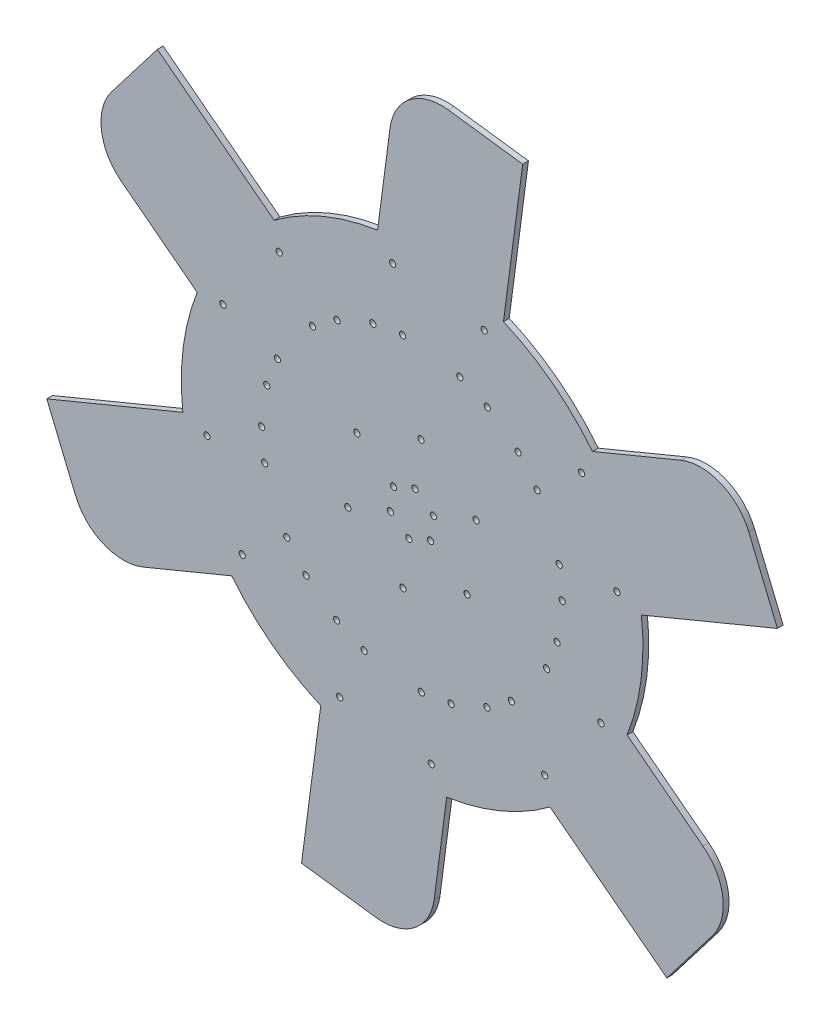
SolidWorks part; units mm, degrees
note: '?' marks a value the reader was unsure of.
ref_plane "Front Plane" through (0, 0, 0) normal (0, 0, 1) x (1, 0, 0)
ref_plane "Top Plane" through (0, 0, 0) normal (0, 1, 0) x (1, 0, 0)
ref_plane "Right Plane" through (0, 0, 0) normal (1, 0, 0) x (0, 0, -1)
sketch "Sketch1" plane through (0, 0, 0) normal (0, 0, 1) x (1, 0, 0)
  circle A0 centre (0, 0) radius 127
  dimension "D1" = 254
extrude "Boss-Extrude1" add sketch "Sketch1" along normal blind 3.175
sketch "Sketch2" plane through (0, 0, 0) normal (0, 0, 1) x (1, 0, 0)
  line L0 (0, 0) -> (117.3327, 48.6008) construction
  circle A0 centre (0, 0) radius 82.55 construction
  circle A1 centre (0, 0) radius 114.3 construction
  point P0 (11.7333, 4.8601)
  point P3 (80.9178, 16.3343)
  point P5 (58.2494, 58.4937)
  point P6 (82.5498, -0.1727)
  point P7 (112.6792, 19.1805)
  point P8 (93.2389, 66.1136)
  point P10 (68.7676, 45.6675)
  point P11 (35.1998, 14.5802)
  dimension "D1" = 12.7
  dimension "D3" = 165.1
  dimension "D4" = 228.6
  dimension "D6" = 31.75
  dimension "D2" = 63.5
  dimension "D5" = 50.8
  dimension "D7" = 38.1
hole_wizard "M3 Clearance Hole1" positions "Sketch3" profile "Sketch4" hole size "M3" standard "ANSI Metric" end condition through all
sketch "Sketch3" plane through (0, 0, 0) normal (0, 0, -1) x (-1, 0, 0)
  point P0 (-58.2494, 58.4937)
  point P3 (-82.5498, -0.1727)
  point P6 (-93.2389, 66.1136)
  point P9 (-112.6792, 19.1805)
  point P12 (-11.7333, 4.8601)
  point P16 (-68.7676, 45.6675)
  point P19 (-80.9178, 16.3343)
  point P22 (-35.1998, 14.5802)
sketch "Sketch4" plane through (58.2494, 58.4937, 0) normal (1, 0, 0) x (0, 1, 0)
  line L0 (0, 0) -> (0, 3.175)
  line L1 (0, 3.175) -> (1.7, 3.175)
  line L2 (1.7, 3.175) -> (1.7, 0)
  line L5 (1.7, 0) -> (0, 0)
  line L11 (0, -6.35) -> (0, 107.95) construction
  dimension "Thru Hole Dia." = 3.4
  dimension "Thru Hole Depth" = 3.175
ref_axis "Axis1" through (0, 0, -0.1588) along (0, 0, 1)?
pattern_circular "CirPattern1" count 6 over 360 about axis through (-0.0975, -0.0404, 0) along (0, 0, 1) of "M3 Clearance Hole1"
sketch "Sketch6" plane through (0, 0, 0) normal (0, 0, -1) x (-1, 0, 0)
  line L1 (-97.9793, 78.7306) -> (-147.8457, 99.3859)
  line L2 (-185.1808, 83.9212) -> (-200.976, 45.7881)
  line L3 (-200.976, 45.7881) -> (-124.7098, 14.1976)
  line L4 (-124.7098, 14.1976) -> (-97.9793, 78.7306)
  line L5 (0, 0) -> (-117.3327, 48.6008) construction
  arc A0 (-185.1808, 83.9212) -> (-147.8457, 99.3859) centre (-158.7809, 72.9861) cw
  dimension "D5" = 28.575
  dimension "D1" = 69.85
  dimension "8" = 203.2
  dimension "D4" = 35.2425
extrude "Boss-Extrude2" add sketch "Sketch6" against normal up to surface (3.175 mm away) up to face at (40.4907, 69.9959, 3.175)
pattern_circular "CirPattern2" count 6 over 360 about axis through (0, 0, 0) along (0, 0, 1) of "Boss-Extrude2"
